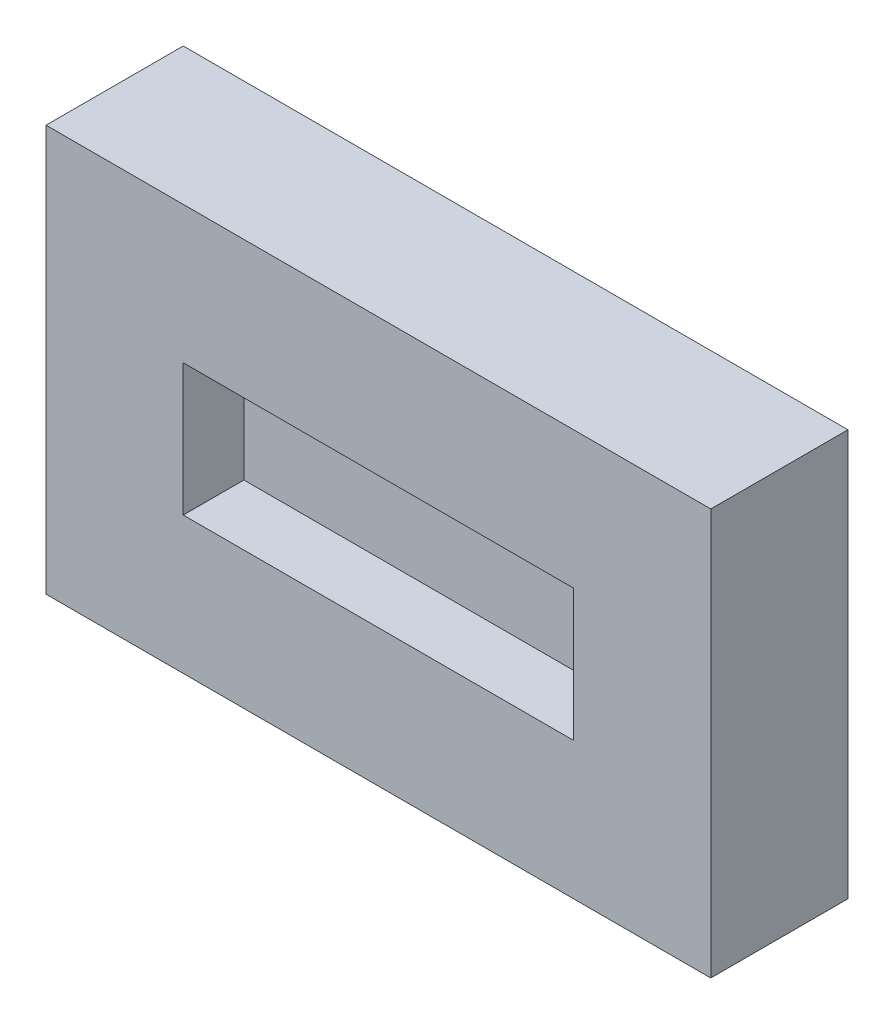
SolidWorks part; units mm, degrees
ref_plane "Plano frontal" through (0, 0, 0) normal (0, 0, 1) x (1, 0, 0)
ref_plane "Plano superior" through (0, 0, 0) normal (0, 1, 0) x (1, 0, 0)
ref_plane "Plano direito" through (0, 0, 0) normal (1, 0, 0) x (0, 0, -1)
sketch "Esboço1" plane through (0, 0, 0) normal (0, 0, 1) x (1, 0, 0)
  line L1 (185, 62.5) -> (-185, 62.5)
  line L2 (185, 62.5) -> (185, -62.5)
  line L3 (185, -62.5) -> (-185, -62.5)
  line L4 (-185, 62.5) -> (-185, -62.5)
  line L5 (185, 62.5) -> (-185, -62.5) construction
  line L6 (185, -62.5) -> (-185, 62.5) construction
  point P0 (0, 0)
  dimension "D1" = 125
  dimension "D2" = 370
extrude "Ressalto-extrusão1" add sketch "Esboço1" along normal blind 7.5 and the other way blind 7.5
sketch "Esboço3" plane through (0, 0, 0) normal (0, 0, 1) x (1, 0, 0)
  line L4 (-185, 62.5) -> (-185, -62.5)
  line L5 (-185, -62.5) -> (185, -62.5)
  line L6 (185, -62.5) -> (185, 62.5)
  line L7 (185, 62.5) -> (-185, 62.5)
  line L8 (-185, 62.5) -> (-185, -62.5)
  line L9 (-185, -62.5) -> (185, -62.5)
  line L10 (185, -62.5) -> (185, 62.5)
  line L11 (185, 62.5) -> (-185, 62.5)
  line L16 (-315, 192.5) -> (-315, -192.5)
  line L17 (-315, -192.5) -> (315, -192.5)
  line L18 (315, -192.5) -> (315, 192.5)
  line L19 (315, 192.5) -> (-315, 192.5)
  line L20 (-315, 192.5) -> (-315, -192.5)
  line L21 (-315, -192.5) -> (315, -192.5)
  line L22 (315, -192.5) -> (315, 192.5)
  line L23 (315, 192.5) -> (-315, 192.5)
  dimension "D1" = 0
  dimension "D2" = 130
extrude "Ressalto-extrusão3" add sketch "Esboço3" along normal blind 65 and the other way blind 65 separate body
